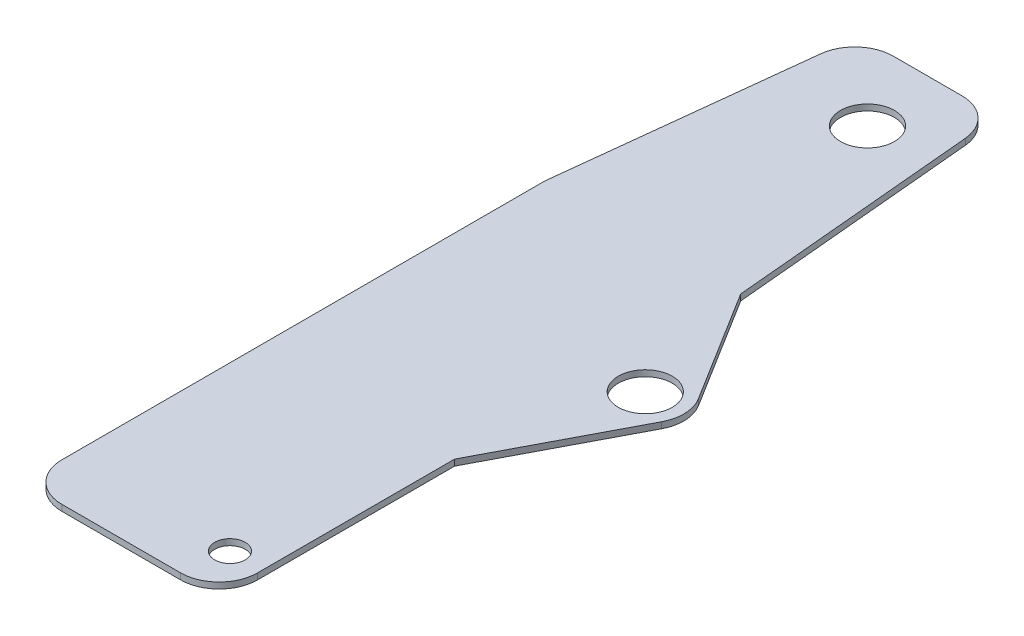
SolidWorks part; units mm, degrees
ref_plane "Front" through (0, 0, 0) normal (0, 0, 1) x (1, 0, 0)
ref_plane "Top" through (0, 0, 0) normal (0, 1, 0) x (1, 0, 0)
ref_plane "Right" through (0, 0, 0) normal (1, 0, 0) x (0, 0, -1)
sketch "Sketch1" plane through (0, 0, 0) normal (0, 1, 0) x (1, 0, 0)
  line L0 (10.4543, 228.6) -> (0, 135.3627)
  line L1 (0, 0) -> (50.8, 0)
  line L2 (0, 0) -> (0, 228.6)
  line L3 (0, 228.6) -> (50.8, 228.6)
  line L4 (50.8, 0) -> (50.8, 228.6)
  line L5 (42.3273, 228.6) -> (50.8, 135.3627)
  line L8 (50.8, 0) -> (24.327, 0)
  line L9 (50.8, 0) -> (50.8, -15)
  line L10 (50.8, -15) -> (24.327, -15)
  line L11 (24.327, 0) -> (24.327, -15)
  line L16 (50.8, 120.6192) -> (50.8, 104.4882)
  line L18 (50.8, 64.8791) -> (50.8, 87.4235)
  circle A2 centre (24.327, 25.5092) radius 5.969
  circle A3 centre (42.3273, 11.2956) radius 3.9601
  circle A12 centre (60.4, 101.001) radius 10
  circle A13 centre (29.5042, 189.5572) radius 7
  dimension "D3" = 20
  dimension "D4" = 11.938
  dimension "D5" = 15
  dimension "D6" = 14
  dimension "D1" = 50.8
  dimension "D2" = 228.6
extrude "Boss-Extrude1" add sketch "Sketch1" along normal blind 1.5875 contours L1 L4 L3 L0 L2 region at (25.4365, 0, -107.5799)
sketch "Sketch4" plane through (0, 0, -228.6) normal (0, 0, -1) x (-1, 0, 0)
  line L1 (-61.3109, 11.9192) -> (4.9615, 11.9192)
  line L2 (-61.3109, 11.9192) -> (-61.3109, -15.8811)
  line L3 (-61.3109, -15.8811) -> (4.9615, -15.8811)
  line L4 (4.9615, 11.9192) -> (4.9615, -15.8811)
extrude "Cut-Extrude2" cut sketch "Sketch4" against normal blind 20
sketch "Sketch5" plane through (0, 0, 0) normal (0, -1, 0) x (1, 0, 0)
  circle A0 centre (24.327, -25.5092) radius 6.6837
extrude "Boss-Extrude2" add sketch "Sketch5" against normal blind 1.5875
fillet "Fillet3" radius 10 1 edges at (44.1447, 0.7937, -208.6)
fillet "Fillet4" radius 10 3 edges at (50.8, 0.7937, 0) (0, 0.7937, 0) (8.2118, 0.7937, -208.6)
sketch "Sketch6" plane through (0, 1.5875, 0) normal (0, 1, 0) x (1, 0, 0)
  line L0 (68.8909, 106.2834) -> (50.8, 135.3627)
  line L1 (50.8, 135.3627) -> (50.8, 103.801)
  line L2 (69.2582, 96.3607) -> (50.8, 61.1242)
  line L3 (50.8, 10) -> (50.8, 98.201) construction
  line L4 (50.8, 61.1242) -> (50.8, 96.3607)
  line L5 (50.8, 96.3607) -> (50.8, 98.201)
  circle A0 centre (60.4, 101.001) radius 10
  line M4 (50.8, 10) -> (50.8, 98.201)
  arc M5 (50.8, 98.201) -> (50.8, 103.801) centre (60.4, 101.001) cw
  line M6 (50.8, 103.801) -> (50.8, 135.3627)
extrude "Boss-Extrude3" add sketch "Sketch6" against normal blind 1.5875 contours A0 L0 M6 | A0 M5 | A0 L2 M4 region at (55.8248, 1.5875, -118.0301) region at (60.4, 1.5875, -101.001) region at (56.0341, 1.5875, -82.1407)
sketch "Sketch7" plane through (0, 1.5875, 0) normal (0, 1, 0) x (1, 0, 0)
  circle A0 centre (60.4, 101.001) radius 7
  dimension "D1" = 14
extrude "Cut-Extrude3" cut sketch "Sketch7" against normal blind 1.5875
equation "\"7i\"=101.6"
